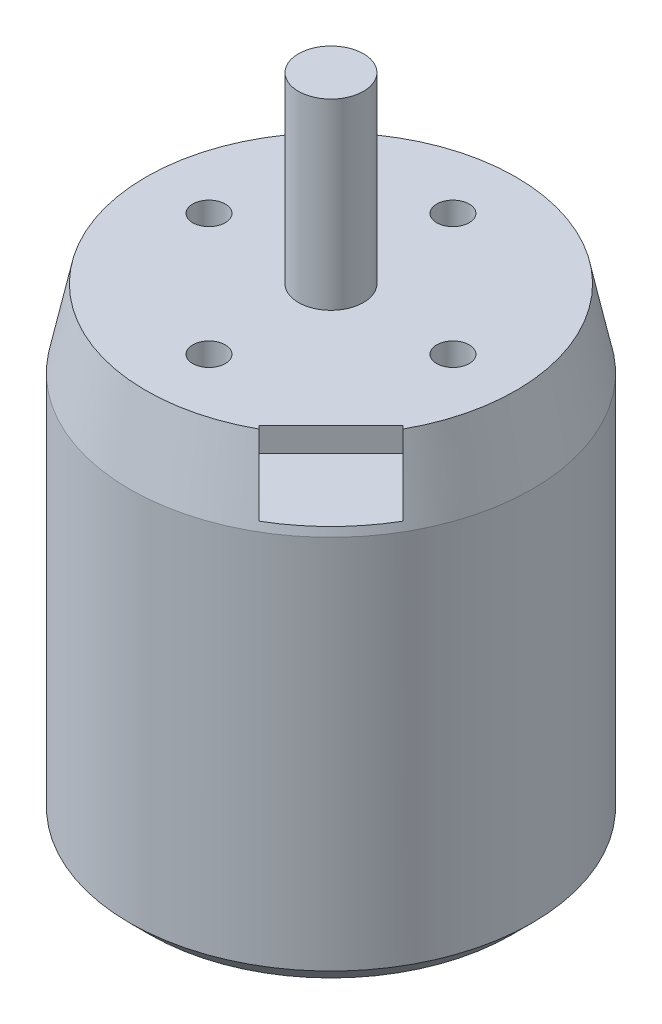
SolidWorks part; units mm, degrees
material "Plain Carbon Steel"
ref_plane "Front Plane" through (0, 0, 0) normal (0, 0, 1) x (1, 0, 0)
ref_plane "Top Plane" through (0, 0, 0) normal (0, 1, 0) x (1, 0, 0)
ref_plane "Right Plane" through (0, 0, 0) normal (1, 0, 0) x (0, 0, -1)
sketch "Sketch1" plane through (0, 0, 0) normal (0, 1, 0) x (1, 0, 0)
  circle A0 centre (0, 0) radius 24.75
  dimension "D1" = 49.5
extrude "Boss-Extrude1" add sketch "Sketch1" along normal blind 58.2
sketch "Sketch2" plane through (0, 58.2, 0) normal (0, 1, 0) x (1, 0, 0)
  circle A0 centre (0, 0) radius 4
  dimension "D1" = 8
extrude "Boss-Extrude2" add sketch "Sketch2" along normal blind 22.5
chamfer "Chamfer1" distance 2.5 angle 45 1 edges at (0, 0, 24.75)
sketch "Sketch3" plane through (0, 0, 0) normal (0, -1, 0) x (1, 0, 0)
  circle A0 centre (0, 0) radius 6.8
  dimension "D1" = 13.6
extrude "Boss-Extrude3" add sketch "Sketch3" along normal blind 2
fillet "Fillet1" radius 0.5 1 edges at (0, 0, -6.8)
sketch "Sketch4" plane through (0, 58.2, 0) normal (0, 1, 0) x (1, 0, 0)
  circle A0 centre (0, 0) radius 15 construction
  circle A1 centre (0, 15) radius 2
  circle A2 centre (15, 0) radius 2
  circle A3 centre (0, -15) radius 2
  circle A4 centre (-15, 0) radius 2
  point P3 (0, 15)
  point P4 (-15, 0)
  point P5 (0, -15)
  point P6 (15, 0)
  dimension "D1" = 30
  dimension "D2" = 4
extrude "Cut-Extrude1" cut sketch "Sketch4" against normal blind 10
sketch "Sketch5" plane through (0, 0, 0) normal (0, -1, 0) x (1, 0, 0)
  circle A0 centre (0, 0) radius 9.875 construction
  circle A1 centre (0, 9.875) radius 1.5
  circle A2 centre (9.875, 0) radius 1.5
  circle A3 centre (0, -9.875) radius 1.5
  circle A4 centre (-9.875, 0) radius 1.5
  dimension "D1" = 19.75
  dimension "D2" = 3
extrude "Cut-Extrude2" cut sketch "Sketch5" against normal blind 5
chamfer "Chamfer2" distance 9.5 distance2 2 1 edges at (0, 58.2, 24.75) first distance on face at (0, 2.5, 24.75)
sketch "Sketch6" plane through (0, 58.2, 0) normal (0, 1, 0) x (1, 0, 0)
  line L0 (0, -22.75) -> (0, 0) construction
  line L1 (0, 0) -> (22.75, 0) construction
  line L2 (22.75, 0) -> (0, -22.75) construction
  line L3 (0, 0) -> (16.0867, -16.0867) construction
  line L4 (19.5161, -10.6773) -> (10.6773, -19.5161)
  line L5 (19.5161, -10.6773) -> (26.5872, -17.7484)
  line L6 (10.6773, -19.5161) -> (17.7484, -26.5872)
  line L7 (26.5872, -17.7484) -> (17.7484, -26.5872)
  circle A0 centre (0, 0) radius 22.75 construction
  dimension "D1" = 1.4
  dimension "D2" = 12.5
  dimension "D3" = 10
extrude "Cut-Extrude3" cut sketch "Sketch6" against normal blind 8.5
sketch "Sketch7" plane through (15.0967, 0, 15.0967) normal (0.7071, 0, 0.7071) x (0.7071, 0, -0.7071)
  line L0 (6.25, 49.7) -> (6.25, 58.2) construction
  line L1 (-6.25, 49.7) -> (6.25, 49.7)
  line L2 (-6.25, 49.7) -> (-6.25, 55.2)
  line L3 (-6.25, 55.2) -> (6.25, 55.2)
  line L4 (6.25, 49.7) -> (6.25, 55.2)
  line L5 (-6.25, 49.7) -> (6.25, 55.2) construction
  line L6 (-6.25, 55.2) -> (6.25, 49.7) construction
  line L7 (6.25, 58.2) -> (-6.25, 58.2) construction
  point P4 (0, 52.45)
  dimension "D1" = 3
extrude "Cut-Extrude4" cut sketch "Sketch7" against normal blind 8.5
